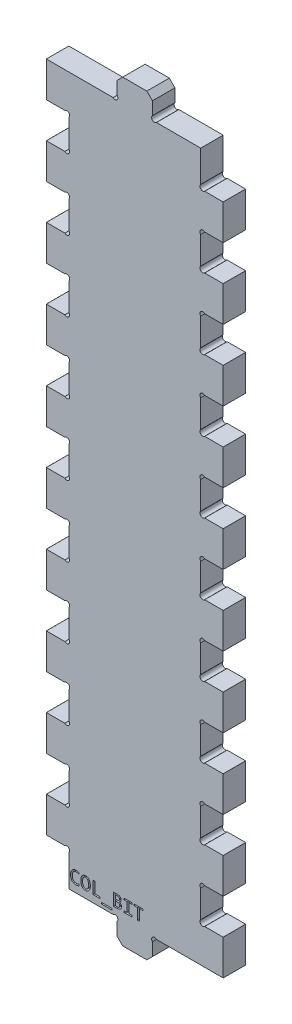
SolidWorks part; units mm, degrees
material "PVC Rigid"
ref_plane "Front Plane" through (0, 0, 0) normal (0, 0, 1) x (1, 0, 0)
ref_plane "Top Plane" through (0, 0, 0) normal (0, 1, 0) x (1, 0, 0)
ref_plane "Right Plane" through (0, 0, 0) normal (1, 0, 0) x (0, 0, -1)
sketch "Model" [suppressed]
  dimension "D3" = 0.7937
  dimension "D1" = 10
  dimension "D2" = 10
sketch "Sketch1" plane through (0, 0, 0) normal (0, 0, 1) x (1, 0, 0)
  line L1 (0, 0) -> (50, 0)
  line L2 (0, 0) -> (0, 200.0001)
  line L3 (0, 200.0001) -> (50, 200.0001)
  line L4 (50, 0) -> (50, 200.0001)
  dimension "D1" = 200.0001
  dimension "D2" = 50
extrude "Boss-Extrude1" add sketch "Sketch1" along normal blind 6.35
sketch "Sketch2" plane through (0, 0, 0) normal (0, 0, 1) x (1, 0, 0)
  line L0 (0, 100.0001) -> (50, 100.0001) construction
  line L1 (50, 200.0001) -> (0, 200.0001) construction
  line L2 (25, 200.0001) -> (25, 203.1751) construction
  line L3 (20, 206.3501) -> (30, 206.3501)
  line L4 (20, 206.3501) -> (20, 200.0001)
  line L5 (20, 200.0001) -> (30, 200.0001)
  line L6 (30, 206.3501) -> (30, 200.0001)
  line L7 (20, 206.3501) -> (30, 200.0001) construction
  line L8 (20, 200.0001) -> (30, 206.3501) construction
  line L9 (0, 200.0001) -> (0, 0) construction
  line L10 (50, 0) -> (50, 200.0001) construction
  line L11 (20, 0) -> (30, -6.35) construction
  line L12 (20, -6.35) -> (30, 0) construction
  line L13 (25, 0) -> (25, -3.175) construction
  line L14 (30, -6.35) -> (30, 0)
  line L15 (20, 0) -> (30, 0)
  line L16 (20, -6.35) -> (20, 0)
  line L17 (20, -6.35) -> (30, -6.35)
  dimension "D1" = 6.35
  dimension "D2" = 10
extrude "Boss-Extrude2" add sketch "Sketch2" along normal blind 6.35
sketch "Sketch3" plane through (0, 0, 6.35) normal (0, 0, 1) x (1, 0, 0)
  line L0 (25, 206.3501) -> (25, -6.35) construction
  line L1 (30, 206.3501) -> (20, 206.3501) construction
  line L2 (20, -6.35) -> (30, -6.35) construction
  line L3 (6.35, 200.0001) -> (6.35, 0) construction
  line L4 (20, 200.0001) -> (0, 200.0001) construction
  line L5 (0, 0) -> (20, 0) construction
  line L6 (0, 200.0001) -> (0, 0) construction
  line L7 (6.35, 0) -> (0, 0)
  line L8 (6.35, 0) -> (6.35, 10)
  line L9 (6.35, 10) -> (0, 10)
  line L10 (0, 0) -> (0, 10)
  line L11 (50, 0) -> (50, 10)
  line L12 (43.65, 10) -> (50, 10)
  line L13 (43.65, 0) -> (43.65, 10)
  line L14 (43.65, 0) -> (50, 0)
  dimension "D1" = 6.35
  dimension "D2" = 10
extrude "Cut-Extrude1" [suppressed] cut sketch "Sketch3" against normal blind 6.35
pattern_linear "LPattern2" [suppressed] count 10 spacing 20 of bodies 108
sketch "Sketch4" [suppressed] plane through (0, 0, 6.35) normal (0, 0, 1) x (1, 0, 0)
  line L0 (0, 10) -> (6.35, 0) construction
  line L1 (6.35, 10) -> (5.2275, 10) construction
  line L2 (0.5613, 0.5613) -> (5.7887, 0.5613) construction
  line L3 (0.5613, 0.5613) -> (0.5613, 9.4387) construction
  line L4 (0.5613, 9.4387) -> (5.7887, 9.4387) construction
  line L5 (5.7887, 0.5613) -> (5.7887, 9.4387) construction
  line L6 (0.5613, 0.5613) -> (5.7887, 9.4387) construction
  line L7 (0.5613, 9.4387) -> (5.7887, 0.5613) construction
  line L8 (6.35, 10) -> (0, 10) construction
  line L9 (6.35, 10) -> (6.35, 8.8775) construction
  line L10 (6.35, 0) -> (6.35, 10) construction
  line L11 (25, 206.3501) -> (25, -6.35) construction
  line L12 (30, 206.3501) -> (20, 206.3501) construction
  line L13 (20, -6.35) -> (30, -6.35) construction
  line L14 (44.2113, 9.4387) -> (44.2113, 20.5613) construction
  line L15 (43.65, 10) -> (43.65, 8.8775) construction
  line L16 (49.4387, 9.4387) -> (44.2113, 0.5613) construction
  line L17 (49.4387, 0.5613) -> (44.2113, 9.4387) construction
  line L18 (44.2113, 0.5613) -> (44.2113, 9.4387) construction
  line L19 (49.4387, 9.4387) -> (44.2113, 9.4387) construction
  line L20 (49.4387, 0.5613) -> (49.4387, 9.4387) construction
  line L21 (49.4387, 0.5613) -> (44.2113, 0.5613) construction
  line L22 (43.65, 10) -> (44.7725, 10) construction
  line L23 (5.7887, 9.4387) -> (5.7887, 20.5613) construction
  line L24 (50, 10) -> (43.65, 0) construction
  circle A0 centre (5.7887, 9.4387) radius 0.7938
  circle A4 centre (5.7887, 20.5613) radius 0.7938
  circle A7 centre (44.2113, 20.5613) radius 0.7937
  circle A8 centre (44.2113, 9.4387) radius 0.7937
  point P4 (3.175, 5)
  point P40 (46.825, 5)
  dimension "D1" = 1.5875
extrude "Cut-Extrude3" [suppressed] cut sketch "Sketch4" against normal blind 6.35
pattern_linear "LPattern3" [suppressed] count 9 spacing 20 of bodies 112
sketch "Sketch8" plane through (0, 0, 6.35) normal (0, 0, 1) x (1, 0, 0)
  line L0 (6.35, 200.0001) -> (6.35, 0) construction
  line L1 (20, 200.0001) -> (0, 200.0001) construction
  line L2 (0, 0) -> (20, 0) construction
  line L3 (0, 200.0001) -> (0, 0) construction
  line L4 (43.65, 200.0001) -> (43.65, 0) construction
  line L5 (0, 0) -> (6.35, 0)
  line L6 (0, 0) -> (0, 10)
  line L7 (0, 10) -> (6.35, 10)
  line L8 (6.35, 0) -> (6.35, 10)
  line L9 (50, 200.0001) -> (30, 200.0001) construction
  line L10 (30, 0) -> (50, 0) construction
  line L11 (50, 0) -> (50, 200.0001) construction
  line L12 (43.65, 10) -> (50, 10)
  line L13 (43.65, 10) -> (43.65, 20)
  line L14 (43.65, 20) -> (50, 20)
  line L15 (50, 10) -> (50, 20)
  dimension "D1" = 6.35
  dimension "D2" = 10
  dimension "D3" = 10
  dimension "D4" = 6.35
  dimension "D5" = 10
extrude "Cut-Extrude6" cut sketch "Sketch8" against normal through all
pattern_linear "LPattern4" count 10 spacing 20 along (0, 1, 0) of "Cut-Extrude6"
sketch "Sketch9" plane through (0, 0, 6.35) normal (0, 0, 1) x (1, 0, 0)
  line L0 (0, 30) -> (6.35, 20) construction
  line L1 (6.35, 30) -> (5.2275, 30) construction
  line L2 (0.5613, 20.5613) -> (5.7887, 20.5613) construction
  line L3 (0.5613, 20.5613) -> (0.5613, 29.4388) construction
  line L4 (0.5613, 29.4388) -> (5.7887, 29.4388) construction
  line L5 (5.7887, 20.5613) -> (5.7887, 29.4388) construction
  line L6 (0.5613, 20.5613) -> (5.7887, 29.4388) construction
  line L7 (0.5613, 29.4388) -> (5.7887, 20.5613) construction
  line L8 (6.35, 30) -> (0, 30) construction
  line L9 (6.35, 30) -> (6.35, 28.8775) construction
  line L10 (6.35, 20) -> (6.35, 30) construction
  line L11 (43.65, 20) -> (50, 10) construction
  line L12 (43.65, 20) -> (44.7725, 20) construction
  line L13 (44.2113, 10.5613) -> (49.4387, 10.5613) construction
  line L14 (44.2113, 10.5613) -> (44.2113, 19.4387) construction
  line L15 (44.2113, 19.4387) -> (49.4387, 19.4387) construction
  line L16 (49.4387, 10.5613) -> (49.4387, 19.4387) construction
  line L17 (44.2113, 10.5613) -> (49.4387, 19.4387) construction
  line L18 (44.2113, 19.4387) -> (49.4387, 10.5613) construction
  line L19 (50, 20) -> (43.65, 20) construction
  line L20 (43.65, 20) -> (43.65, 18.8775) construction
  line L21 (43.65, 20) -> (43.65, 10) construction
  line L22 (50, 20) -> (50, 30) construction
  circle A0 centre (5.7887, 29.4388) radius 0.7938
  circle A1 centre (5.7887, 20.5613) radius 0.7938
  circle A2 centre (44.2113, 19.4387) radius 0.7937
  circle A3 centre (44.2113, 10.5613) radius 0.7937
  point P4 (3.175, 25)
  point P23 (46.825, 15)
  dimension "D1" = 1.5875
  dimension "D2" = 10
extrude "Cut-Extrude7" cut sketch "Sketch9" against normal through all
pattern_linear "LPattern5" count 9 spacing 20 along (0, 1, 0) of "Cut-Extrude7"
sketch "Sketch10" plane through (0, 0, 6.35) normal (0, 0, 1) x (1, 0, 0)
  line L0 (0, 10) -> (6.35, 0) construction
  line L1 (5.2275, 10) -> (6.35, 10) construction
  line L2 (0.5613, 0.5613) -> (5.7887, 0.5613) construction
  line L3 (0.5613, 0.5613) -> (0.5613, 9.4387) construction
  line L4 (0.5613, 9.4387) -> (5.7887, 9.4387) construction
  line L5 (5.7887, 0.5613) -> (5.7887, 9.4387) construction
  line L6 (0.5613, 0.5613) -> (5.7887, 9.4387) construction
  line L7 (0.5613, 9.4387) -> (5.7887, 0.5613) construction
  line L8 (6.35, 10) -> (0, 10) construction
  line L9 (6.35, 10) -> (6.35, 8.8775) construction
  line L10 (6.35, 0) -> (6.35, 10) construction
  line L11 (6.35, 5) -> (3.175, 5) construction
  line L12 (0, 200.0001) -> (50, 0) construction
  line L13 (43.65, 200.0001) -> (50, 190.0001) construction
  line L14 (44.7725, 190.0001) -> (43.65, 190.0001) construction
  line L15 (44.2113, 190.5614) -> (49.4387, 190.5614) construction
  line L16 (44.2113, 190.5614) -> (44.2113, 199.4388) construction
  line L17 (44.2113, 199.4388) -> (49.4387, 199.4388) construction
  line L18 (49.4387, 190.5614) -> (49.4387, 199.4388) construction
  line L19 (44.2113, 190.5614) -> (49.4387, 199.4388) construction
  line L20 (44.2113, 199.4388) -> (49.4387, 190.5614) construction
  line L21 (43.65, 190.0001) -> (50, 190.0001) construction
  line L22 (43.65, 190.0001) -> (43.65, 191.1226) construction
  line L23 (43.65, 200.0001) -> (43.65, 190.0001) construction
  circle A0 centre (5.7887, 9.4387) radius 0.7938
  circle A2 centre (44.2113, 190.5614) radius 0.7937
  point P4 (3.175, 5)
  point P28 (46.825, 195.0001)
  dimension "D1" = 1.5875
  dimension "D2" = 1.5875
extrude "Cut-Extrude8" cut sketch "Sketch10" against normal through all
chamfer "Chamfer1" distance 1.5875 angle 45 4 edges at (30, -6.35, 3.175) (20, -6.35, 3.175) (20, 206.3501, 3.175) (30, 206.3501, 3.175)
sketch "Sketch5" [suppressed] plane through (0, 0, 6.35) normal (0, 0, 1) x (1, 0, 0)
  line L0 (6.35, 180.0001) -> (0, 190.0001) construction
  line L1 (6.35, 190.0001) -> (5.2275, 190.0001) construction
  line L2 (0.5613, 180.5614) -> (5.7887, 180.5614) construction
  line L3 (0.5613, 180.5614) -> (0.5613, 189.4388) construction
  line L4 (0.5613, 189.4388) -> (5.7887, 189.4388) construction
  line L5 (5.7887, 180.5614) -> (5.7887, 189.4388) construction
  line L6 (0.5613, 180.5614) -> (5.7887, 189.4388) construction
  line L7 (0.5613, 189.4388) -> (5.7887, 180.5614) construction
  line L8 (6.35, 190.0001) -> (0, 190.0001) construction
  line L9 (6.35, 190.0001) -> (6.35, 188.8776) construction
  line L10 (6.35, 181.1226) -> (6.35, 190.0001) construction
  line L15 (25, 206.3501) -> (25, -6.35) construction
  line L16 (28.4125, 206.3501) -> (21.5875, 206.3501) construction
  line L17 (21.5875, -6.35) -> (28.4125, -6.35) construction
  line L20 (43.65, 190.0001) -> (43.65, 188.8776) construction
  line L21 (49.4387, 189.4388) -> (44.2113, 180.5614) construction
  line L22 (49.4387, 180.5614) -> (44.2113, 189.4388) construction
  line L23 (44.2113, 180.5614) -> (44.2113, 189.4388) construction
  line L24 (49.4387, 189.4388) -> (44.2113, 189.4388) construction
  line L25 (49.4387, 180.5614) -> (49.4387, 189.4388) construction
  line L26 (49.4387, 180.5614) -> (44.2113, 180.5614) construction
  line L27 (43.65, 190.0001) -> (44.7725, 190.0001) construction
  line L28 (43.65, 180.0001) -> (50, 190.0001) construction
  line L29 (50, 100.0001) -> (0, 100.0001) construction
  arc A0 (5.2275, 180.0001) -> (6.35, 181.1226) centre (5.7887, 180.5614) ccw construction
  circle A1 centre (5.7887, 189.4388) radius 0.7938
  circle A4 centre (44.2113, 189.4388) radius 0.7937
  point P6 (3.175, 185.0001)
  point P51 (46.825, 185.0001)
  point P56 (25, 100.0001)
  dimension "D1" = 1.5875
extrude "Cut-Extrude4" [suppressed] cut sketch "Sketch5" against normal blind 6.35
sketch "Sketch11" plane through (0, 0, 0) normal (0, 0, 1) x (1, 0, 0)
  line L0 (28.4125, 206.3501) -> (21.5875, 206.3501) construction
  line L11 (20, 201.1226) -> (20, 200.0001) construction
  line L13 (20, 200.0001) -> (18.8775, 200.0001) construction
  line L15 (25, 206.3501) -> (25, -6.35) construction
  line L18 (30, 200.0001) -> (31.1225, 200.0001) construction
  line L19 (30, 201.1226) -> (30, 200.0001) construction
  line L29 (50, 100.0001) -> (0, 100.0001) construction
  circle A2 centre (19.4387, 200.5614) radius 0.7937
  circle A3 centre (30.5613, 200.5614) radius 0.7937
  circle A5 centre (19.4387, -0.5613) radius 0.7937
  circle A6 centre (30.5613, -0.5613) radius 0.7937
  point P56 (25, 100.0001)
  dimension "D1" = 1.5875
  dimension "D2" = 19.4387
  dimension "D3" = 100.0001
  dimension "D4" = 200.0001
extrude "Cut-Extrude10" cut sketch "Sketch11" along normal through all
sketch "Sketch6" [suppressed] plane through (0, 0, 6.35) normal (0, 0, 1) x (1, 0, 0)
  line L0 (6.604, 2.032) -> (43.65, 2.032) construction
  line L1 (43.65, 10) -> (43.65, 0) construction
  line L2 (6.35, 0) -> (18.8775, 0) construction
  line L4 (0, 20) -> (0, 10) construction
  text T0 "COL_BIT" font "Consolas" height 3.5
  dimension "D1" = 2.032
  dimension "D2" = 6.604
extrude "Cut-Extrude5" [suppressed] cut sketch "Sketch6" against normal blind 2.54
sketch "Sketch12" plane through (0, 0, 6.35) normal (0, 0, 1) x (1, 0, 0)
  line L0 (6.604, 2.032) -> (40.0372, 2.032) construction
  text T0 "COL_BIT" font "Consolas" height 3.5
  dimension "D1" = 2.032
  dimension "D2" = 6.604
extrude "Cut-Extrude11" cut sketch "Sketch12" against normal blind 2.54
sketch "Sketch13" [suppressed] plane through (0, 0, 6.35) normal (0, 0, 1) x (1, 0, 0)
  line L0 (0, 10) -> (6.35, 0) construction
  line L1 (5.2275, 10) -> (0, 10) construction
  line L2 (6.337, -0.0127) -> (0.013, -0.0127)
  line L3 (6.337, -0.0127) -> (6.337, 10.0127)
  line L4 (6.337, 10.0127) -> (0.013, 10.0127)
  line L5 (0.013, -0.0127) -> (0.013, 10.0127)
  line L6 (6.337, -0.0127) -> (0.013, 10.0127) construction
  line L7 (6.337, 10.0127) -> (0.013, -0.0127) construction
  line L8 (25, 206.3501) -> (25, -6.35) construction
  line L9 (28.4125, 206.3501) -> (21.5875, 206.3501) construction
  line L10 (21.5875, -6.35) -> (28.4125, -6.35) construction
  line L11 (43.663, 10.0127) -> (49.987, -0.0127) construction
  line L12 (43.663, -0.0127) -> (49.987, 10.0127) construction
  line L13 (50, 10) -> (43.65, 0) construction
  line L14 (49.987, -0.0127) -> (49.987, 10.0127)
  line L15 (43.663, 10.0127) -> (49.987, 10.0127)
  line L16 (43.663, -0.0127) -> (43.663, 10.0127)
  line L17 (43.663, -0.0127) -> (49.987, -0.0127)
  arc A0 (6.35, 8.8775) -> (5.2275, 10) centre (5.7887, 9.4387) ccw construction
  point P4 (3.175, 5)
  point P26 (46.825, 5)
  dimension "D1" = 0.0127
extrude "Cut-Extrude12" [suppressed] cut sketch "Sketch13" against normal through all
pattern_linear "LPattern6" [suppressed] count 10 spacing 20 of bodies 123
sketch "Sketch14" plane through (0, 0, 6.35) normal (0, 0, 1) x (1, 0, 0)
  line L0 (0, 10) -> (6.35, 0) construction
  line L1 (5.2275, 10) -> (0, 10) construction
  line L2 (0.013, -0.0127) -> (6.337, -0.0127)
  line L3 (0.013, -0.0127) -> (0.013, 10.0127)
  line L4 (0.013, 10.0127) -> (6.337, 10.0127)
  line L5 (6.337, -0.0127) -> (6.337, 10.0127)
  line L6 (0.013, -0.0127) -> (6.337, 10.0127) construction
  line L7 (0.013, 10.0127) -> (6.337, -0.0127) construction
  line L8 (43.65, 20) -> (50, 10) construction
  line L9 (50, 20) -> (44.7725, 20) construction
  line L10 (43.663, 9.9873) -> (49.987, 9.9873)
  line L11 (43.663, 9.9873) -> (43.663, 20.0127)
  line L12 (43.663, 20.0127) -> (49.987, 20.0127)
  line L13 (49.987, 9.9873) -> (49.987, 20.0127)
  line L14 (43.663, 9.9873) -> (49.987, 20.0127) construction
  line L15 (43.663, 20.0127) -> (49.987, 9.9873) construction
  arc A0 (6.35, 8.8775) -> (5.2275, 10) centre (5.7887, 9.4387) ccw construction
  arc A1 (44.7725, 20) -> (43.65, 18.8775) centre (44.2113, 19.4387) ccw construction
  point P4 (3.175, 5)
  point P9 (46.825, 15)
  dimension "D1" = 0.0127
  dimension "D2" = 0.0127
extrude "Cut-Extrude13" cut sketch "Sketch14" against normal through all
pattern_linear "LPattern7" count 10 spacing 20 along (0, 1, 0) of "Cut-Extrude13"
equation "\"tHeight\"=0.25"
equation "\"D1@Sketch2\"=\"tHeight\""
equation "\"tWidth\"=0.393701"
equation "\"D2@Sketch2\"=\"tWidth\""
equation "\"D1@Sketch1\"=\"tWidth\"*20"
equation "\"D1@Sketch3\"=\"tHeight\""
equation "\"D2@Sketch3\"=\"tWidth\""
equation "\"D3@LPattern1\"=\"tWidth\"*2"
equation "\"D3@LPattern2\"=\"tWidth\"*2"
equation "\"D3@LPattern3\"=\"tWidth\"*2"
equation "\"D1@Sketch8\"=\"tHeight\""
equation "\"D2@Sketch8\"=\"tWidth\""
equation "\"D3@Sketch8\"=\"tWidth\""
equation "\"D4@Sketch8\"=\"tHeight\""
equation "\"D5@Sketch8\"=\"tWidth\""
equation "\"D3@LPattern4\"=\"tWidth\"*2"
equation "\"D3@LPattern5\"=\"tWidth\"*2"
equation "\"D2@Sketch9\"=\"tWidth\""
equation "\"tol\"=0.0005"
equation "\"D1@Sketch13\"=\"tol\""
equation "\"D3@LPattern6\"=\"tWidth\"*2"
equation "\"D1@Sketch14\"=\"tol\""
equation "\"D2@Sketch14\"=\"tol\""
